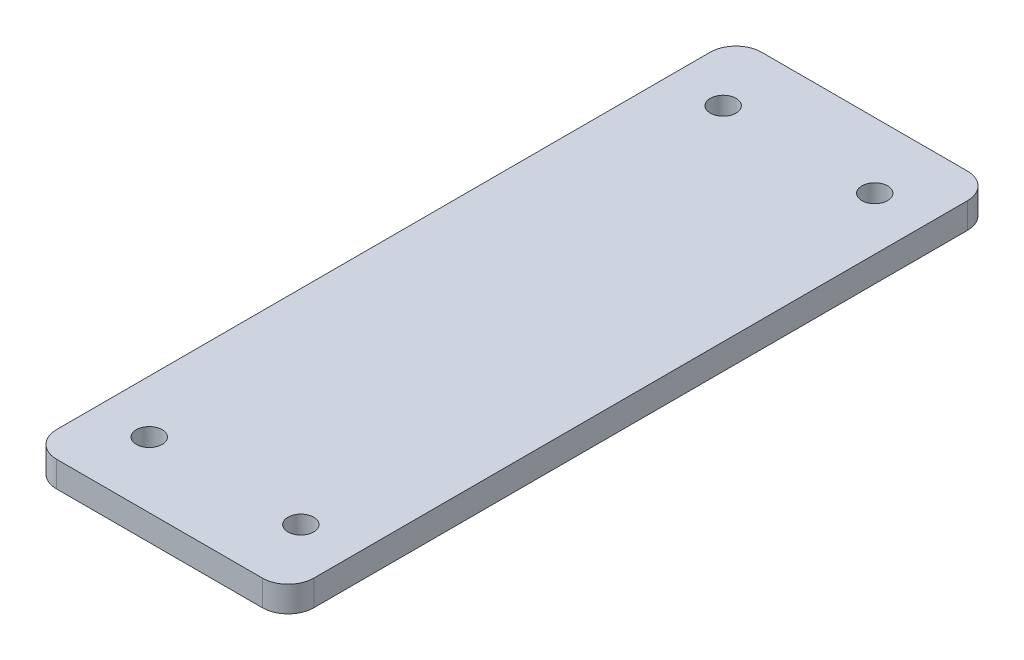
SolidWorks part; units mm, degrees
ref_plane "Front Plane" through (0, 0, 0) normal (0, 0, 1) x (1, 0, 0)
ref_plane "Top Plane" through (0, 0, 0) normal (0, 1, 0) x (1, 0, 0)
ref_plane "Right Plane" through (0, 0, 0) normal (1, 0, 0) x (0, 0, -1)
sketch "Sketch1" plane through (0, 0, 0) normal (0, 1, 0) x (1, 0, 0)
  line L0 (0, 33.4628) -> (0, -42.1291) construction
  line L1 (-39.1744, 0) -> (52.4466, 0) construction
  line L2 (-23.1, -23.1) -> (23.1, -23.1) construction
  line L3 (23.1, -23.1) -> (23.1, 23.1) construction
  line L4 (23.1, 23.1) -> (-23.1, 23.1) construction
  line L5 (-23.1, 23.1) -> (-23.1, -23.1) construction
  line L6 (-23.1, -23.1) -> (23.1, 23.1) construction
  line L7 (-23.1, 23.1) -> (23.1, -23.1) construction
  line L9 (6.5, -42.6342) -> (-6.5, -42.6342) construction
  line L10 (6.5, -42.6342) -> (6.5, 42.6342) construction
  line L11 (6.5, 42.6342) -> (-6.5, 42.6342) construction
  line L12 (-6.5, -42.6342) -> (-6.5, 42.6342) construction
  line L13 (6.5, -42.6342) -> (-6.5, 42.6342) construction
  line L14 (6.5, 42.6342) -> (-6.5, -42.6342) construction
  line L15 (-15, -41.108) -> (15, -41.108) construction
  line L16 (-15, -41.108) -> (-15, 41.108) construction
  line L17 (-15, 41.108) -> (15, 41.108) construction
  line L18 (15, -41.108) -> (15, 41.108) construction
  line L19 (-15, -41.108) -> (15, 41.108) construction
  line L20 (-15, 41.108) -> (15, -41.108) construction
  line L21 (-15, 41.108) -> (15, 41.108) construction
  line L22 (15, 41.108) -> (15, 21.6935) construction
  line L23 (-15, -21.6935) -> (-15, -41.108) construction
  line L24 (-15, -41.108) -> (15, -41.108) construction
  line L25 (15, -41.108) -> (15, -21.6935) construction
  line L27 (-12, -41.108) -> (12, -41.108)
  line L28 (-15, -38.108) -> (-15, 38.108)
  line L29 (-12, 41.108) -> (12, 41.108)
  line L30 (15, -38.108) -> (15, 38.108)
  line L31 (-15, -41.108) -> (15, 41.108) construction
  line L32 (-15, 41.108) -> (15, -41.108) construction
  circle A0 centre (0, 0) radius 23.1 construction
  circle A1 centre (0, 0) radius 9.5 construction
  circle A2 centre (0, 0) radius 12.5 construction
  circle A3 centre (-8.8388, 8.8388) radius 1.5 construction
  circle A4 centre (8.8388, -8.8388) radius 1.5 construction
  circle A5 centre (6.7175, 6.7175) radius 1.5 construction
  circle A6 centre (-6.7175, -6.7175) radius 1.5 construction
  circle A7 centre (0, 0) radius 5 construction
  arc A8 (-17.4471, 15.1396) -> (-17.4471, -15.1396) centre (0, 0) ccw construction
  arc A9 (17.4471, 15.1396) -> (17.4471, -15.1396) centre (0, 0) cw construction
  arc A10 (15, 21.6935) -> (17.4471, 15.1396) centre (25, 21.6935) ccw construction
  arc A11 (-17.4471, 15.1396) -> (-15, 21.6935) centre (-25, 21.6935) ccw construction
  arc A12 (-15, -21.6935) -> (-17.4471, -15.1396) centre (-25, -21.6935) ccw construction
  arc A13 (15, -21.6935) -> (17.4471, -15.1396) centre (25, -21.6935) cw construction
  circle A14 centre (-8.8388, 33.4628) radius 1.5 construction
  circle A15 centre (8.8388, 33.4628) radius 1.5 construction
  circle A16 centre (8.8388, -33.4628) radius 1.5 construction
  circle A17 centre (-8.8388, -33.4628) radius 1.5 construction
  circle A18 centre (-8.8388, 33.4628) radius 1.5
  circle A19 centre (8.8388, 33.4628) radius 1.5
  circle A20 centre (8.8388, -33.4628) radius 1.5
  circle A21 centre (-8.8388, -33.4628) radius 1.5
  arc A22 (15, -38.108) -> (12, -41.108) centre (12, -38.108) cw
  arc A23 (-12, -41.108) -> (-15, -38.108) centre (-12, -38.108) cw
  arc A24 (15, 38.108) -> (12, 41.108) centre (12, 38.108) ccw
  arc A25 (-12, 41.108) -> (-15, 38.108) centre (-12, 38.108) ccw
  point P38 (15, 17.5673)
  point P41 (-15, 17.5673)
  point P54 (0, 0)
  dimension "D1" = 46.2
  dimension "D3" = 10
  dimension "D4" = 10
  dimension "D5" = 10
  dimension "D6" = 10
  dimension "D7" = 3
  dimension "D2" = 13
extrude "Boss-Extrude1" add sketch "Sketch1" along normal blind 3
